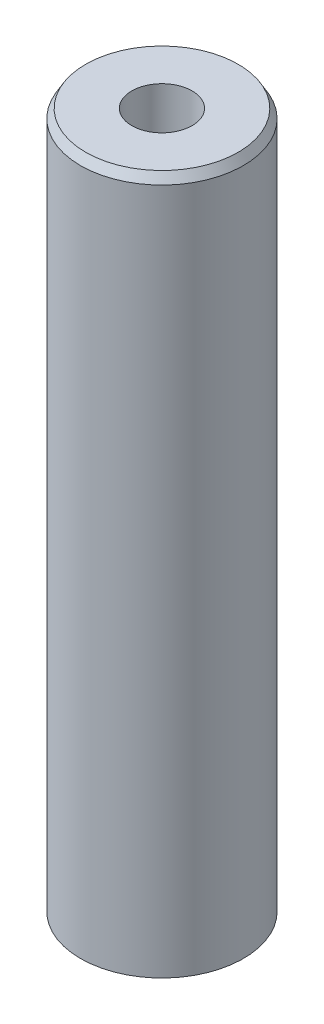
SolidWorks part; units mm, degrees
ref_plane "Front Plane" through (0, 0, 0) normal (0, 0, 1) x (1, 0, 0)
ref_plane "Top Plane" through (0, 0, 0) normal (0, 1, 0) x (1, 0, 0)
ref_plane "Right Plane" through (0, 0, 0) normal (1, 0, 0) x (0, 0, -1)
sketch "Sketch1" plane through (0, 0, 0) normal (0, 1, 0) x (1, 0, 0)
  circle A0 centre (0, 0) radius 27.5
  dimension "SHAFT_OD" = 55
extrude "Boss-Extrude1" add sketch "Sketch1" along normal blind 236.651
sketch "Sketch2" plane through (0, 0, 0) normal (0, 1, 0) x (1, 0, 0)
  circle A0 centre (0, 0) radius 10.1836
  dimension "BORE_D" = 20.3671
extrude "Cut-Extrude1" cut sketch "Sketch2" along normal through all
chamfer "Chamfer1" distance 3.0225 angle 30 2 edges at (0, 236.651, 27.5) (0, 0, 27.5) first distance on face at (0, 236.651, 27.5) first distance on face at (0, 0, 10.1836)
